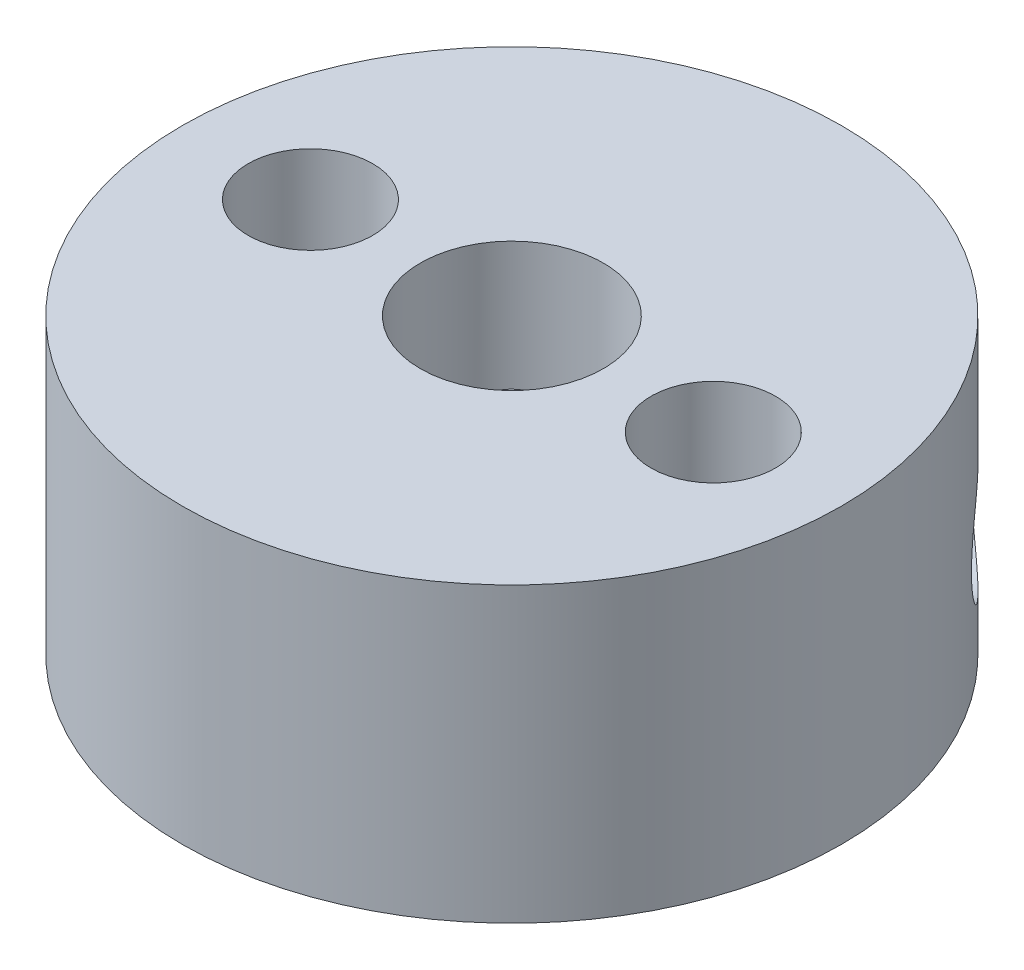
SolidWorks part; units mm, degrees
material "6061 Alloy"
ref_plane "Front Plane" through (0, 0, 0) normal (0, 0, 1) x (1, 0, 0)
ref_plane "Top Plane" through (0, 0, 0) normal (0, 1, 0) x (1, 0, 0)
ref_plane "Right Plane" through (0, 0, 0) normal (1, 0, 0) x (0, 0, -1)
sketch "Sketch1" plane through (0, 0, 0) normal (0, 1, 0) x (1, 0, 0)
  line L0 (-55, 0) -> (55, 0) construction
  line L1 (0, -55) -> (0, 55) construction
  circle A0 centre (0, 0) radius 9
  circle A1 centre (0, 0) radius 2.5
  circle A2 centre (5.5, 0) radius 1.7
  circle A3 centre (-5.5, 0) radius 1.7
  dimension "D1" = 18
  dimension "D2" = 5
  dimension "D3" = 3.4
  dimension "D4" = 5.5
extrude "Boss-Extrude1" add sketch "Sketch1" along normal blind 8 contours A0 | A1 | A2 | A3
ref_axis "Axis1" through (0, 8, 0) along (0, -1, 0)
ref_plane "Plane1" through (0, 0, 0) normal (-0.7071, 0, 0.7071) x (0, -1, 0)
sketch "Sketch2" plane through (0, 0, 0) normal (-0.7071, 0, 0.7071) x (0, -1, 0)
  line L0 (-8, 0) -> (0, 0) construction
  line L1 (0, 55) -> (0, -55) construction
  circle A0 centre (-3, 0) radius 1.5
  dimension "D1" = 3
  dimension "D2" = 3
extrude "Cut-Extrude1" cut sketch "Sketch2" against normal through all
mirror "Mirror1" about plane through (0, 0, 0) normal (1, 0, 0) of "Cut-Extrude1"
